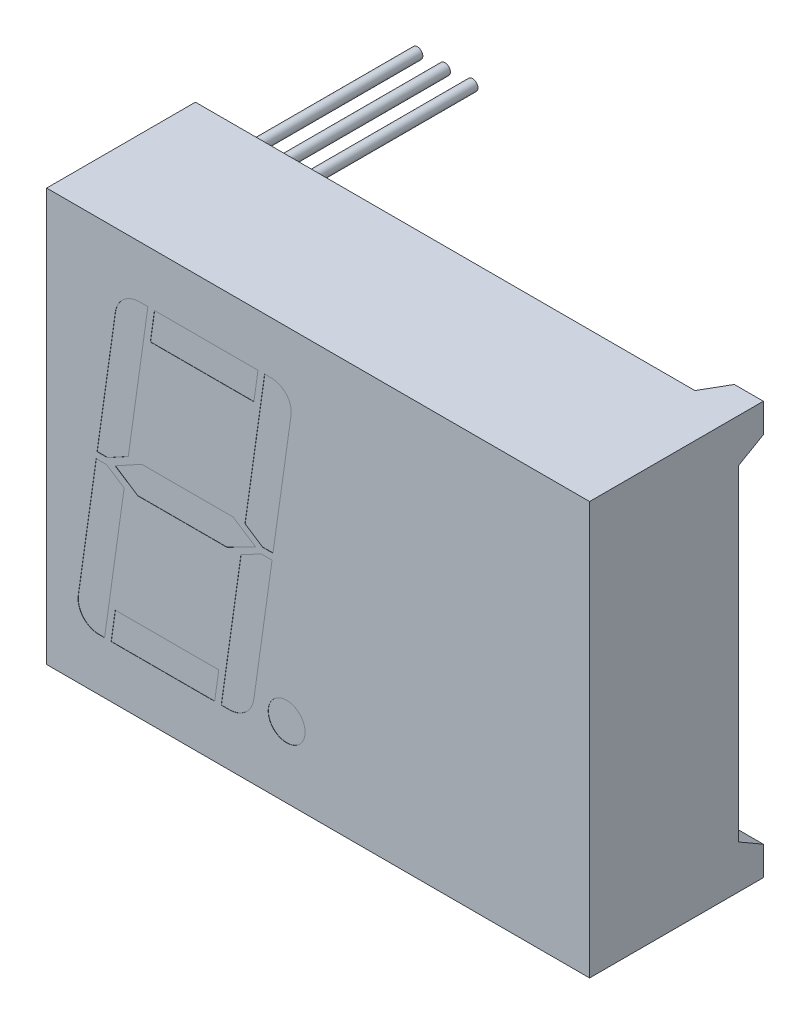
SolidWorks part; units mm, degrees
ref_plane "Plan de face" through (0, 0, 0) normal (0, 0, 1) x (1, 0, 0)
ref_plane "Plan de dessus" through (0, 0, 0) normal (0, 1, 0) x (1, 0, 0)
ref_plane "Plan de droite" through (0, 0, 0) normal (1, 0, 0) x (0, 0, -1)
sketch "Sketch1" plane through (0, 0, 0) normal (0, 0, 1) x (1, 0, 0)
  line L1 (12.5, -9.5) -> (-12.5, -9.5)
  line L2 (12.5, -9.5) -> (12.5, 9.5)
  line L3 (12.5, 9.5) -> (-12.5, 9.5)
  line L4 (-12.5, -9.5) -> (-12.5, 9.5)
  line L5 (12.5, -9.5) -> (-12.5, 9.5) construction
  line L6 (12.5, 9.5) -> (-12.5, -9.5) construction
  point P0 (0, 0)
  dimension "D1" = 25
  dimension "D2" = 19
extrude "Boss-Extrude1" add sketch "Sketch1" along normal blind 8
sketch "Sketch8" plane through (12.5, 0, 0) normal (1, 0, 0) x (0, 0, -1)
  line L0 (0, 0) -> (-8, 0) construction
  line L1 (0, -9.5) -> (0, 9.5) construction
  line L2 (-8, -9.5) -> (-8, 9.5) construction
  line L3 (-1.15, 7.5) -> (-1.15, -7.5)
  line L4 (-1.15, -7.5) -> (0, -8.164)
  line L5 (0, 8.164) -> (0, -8.164)
  line L6 (-8, -9.5) -> (0, -9.5) construction
  line L7 (-1.15, 7.5) -> (0, 8.164)
  point P13 (-1.15, 0)
  dimension "D1" = 1.15
  dimension "D2" = 2
  dimension "D3" = 120
extrude "Cut-Extrude9" cut sketch "Sketch8" against normal up to next
sketch "Sketch6" plane through (0, -9.5, 0) normal (0, -1, 0) x (1, 0, 0)
  line L0 (11.164, 0) -> (10.5, 1.15)
  line L3 (-12.5, 0) -> (12.5, 0) construction
  line L4 (10.5, 1.15) -> (-12.5, 1.15)
  line L7 (-12.5, 8) -> (-12.5, 0) construction
  line L8 (-12.5, 1.15) -> (-12.5, 0)
  line L9 (-12.5, 0) -> (11.164, 0)
  line L10 (12.5, 8) -> (12.5, 0) construction
  dimension "D1" = 2
  dimension "D2" = 120
  dimension "D3" = 1.15
extrude "Cut-Extrude3" cut sketch "Sketch6" against normal up to surface (19 mm away) up to face at (0, 9.5, 4)
sketch "Sketch7" plane through (0, 0, 1.15) normal (0, 0, -1) x (-1, 0, 0)
  line L1 (12.5, 0) -> (-12.5, 0) construction
  line L6 (-12.5, 7.5) -> (-12.5, -7.5) construction
  line L8 (12.5, -9.5) -> (12.5, 9.5) construction
  circle A0 centre (9.96, 7.62) radius 0.25
  circle A1 centre (8.69, 7.62) radius 0.25
  circle A2 centre (11.23, 7.62) radius 0.25
  circle A3 centre (9.96, -7.65) radius 0.25
  circle A4 centre (8.69, -7.65) radius 0.25
  circle A5 centre (11.23, -7.65) radius 0.25
  dimension "D3" = 3
  dimension "D2" = 0.5
  dimension "D1" = 1.27
  dimension "D6" = 7.62
  dimension "D4" = 2
extrude "Boss-Extrude2" add sketch "Sketch7" along normal blind 8.95
sketch "Sketch9" plane through (0, 0, 8) normal (0, 0, 1) x (1, 0, 0)
  line L0 (-12.5, 0) -> (12.5, 0) construction
  line L1 (-12.5, 9.5) -> (-12.5, -9.5) construction
  line L2 (12.5, -9.5) -> (12.5, 9.5) construction
  line L3 (-6.15, 9.5) -> (-6.15, -9.5) construction
  line L4 (12.5, 9.5) -> (-12.5, 9.5) construction
  line L5 (-12.5, -9.5) -> (12.5, -9.5) construction
  line L6 (-9.2022, 7.1) -> (-11.1978, -7.1) construction
  line L7 (-11.1978, -7.1) -> (-3.0978, -7.1) construction
  line L8 (-3.0978, -7.1) -> (-1.1022, 7.1) construction
  line L9 (-1.1022, 7.1) -> (-9.2022, 7.1) construction
  line L10 (-5.1522, 7.1) -> (-7.1478, -7.1) construction
  line L11 (-3.5826, -7.1) -> (-1.5869, 7.1) construction
  line L12 (-1.2919, 5.75) -> (-9.3919, 5.75) construction
  line L13 (-10.7131, -7.1) -> (-8.7174, 7.1) construction
  line L14 (-9.8346, -7.1) -> (-7.8389, 7.1) construction
  line L15 (-4.4611, -7.1) -> (-2.4654, 7.1) construction
  line L16 (-2.9081, -5.75) -> (-11.0081, -5.75) construction
  line L17 (-2.0789, 0.15) -> (-10.1789, 0.15) construction
  line L18 (-2.1211, -0.15) -> (-10.2211, -0.15) construction
  line L19 (-10.1789, 0.15) -> (-9.3389, 6.1268)
  line L20 (-8.2194, 7.1) -> (-7.8389, 7.1)
  line L21 (-7.8389, 7.1) -> (-8.7419, 0.675)
  line L22 (-8.7419, 0.675) -> (-9.6942, 0.15)
  line L23 (-9.6942, 0.15) -> (-10.1789, 0.15)
  line L24 (-2.0789, 0.15) -> (-2.5636, 0.15)
  line L25 (-2.5636, 0.15) -> (-3.3684, 0.675)
  line L26 (-3.3684, 0.675) -> (-2.4654, 7.1)
  line L27 (-2.4654, 7.1) -> (-2.1419, 7.1)
  line L28 (-1.2469, 6.0704) -> (-2.0789, 0.15)
  line L29 (-2.0051, 0.675) -> (-10.1051, 0.675) construction
  line L30 (-2.1949, -0.675) -> (-10.2949, -0.675) construction
  line L31 (-10.2211, -0.15) -> (-9.7364, -0.15)
  line L32 (-9.7364, -0.15) -> (-8.9316, -0.675)
  line L33 (-8.9316, -0.675) -> (-9.8346, -7.1)
  line L34 (-9.8346, -7.1) -> (-10.1004, -7.1)
  line L35 (-11.0451, -6.0132) -> (-10.2211, -0.15)
  line L36 (-2.1211, -0.15) -> (-2.9581, -6.1055)
  line L37 (-4.1022, -7.1) -> (-4.4611, -7.1)
  line L38 (-4.4611, -7.1) -> (-3.5528, -0.6372)
  line L39 (-3.5528, -0.6372) -> (-2.6058, -0.15)
  line L40 (-2.6058, -0.15) -> (-2.1211, -0.15)
  line L41 (-9.3419, -5.75) -> (-4.5743, -5.75)
  line L42 (-4.5743, -5.75) -> (-4.7641, -7.1)
  line L43 (-4.7641, -7.1) -> (-9.5316, -7.1)
  line L44 (-9.5316, -7.1) -> (-9.3419, -5.75)
  line L45 (-7.5359, 7.1) -> (-2.7684, 7.1)
  line L46 (-2.7684, 7.1) -> (-2.9581, 5.75)
  line L47 (-2.9581, 5.75) -> (-7.7257, 5.75)
  line L48 (-7.7257, 5.75) -> (-7.5359, 7.1)
  line L49 (-8.1205, 0.675) -> (-3.9175, 0.675)
  line L50 (-3.9175, 0.675) -> (-2.8828, 0)
  line L51 (-2.8828, 0) -> (-4.1948, -0.675)
  line L52 (-4.1948, -0.675) -> (-8.3102, -0.675)
  line L53 (-8.3102, -0.675) -> (-9.3449, 0)
  line L54 (-9.3449, 0) -> (-8.1205, 0.675)
  circle A0 centre (-1.45, -6.25) radius 0.85
  arc A1 (-9.3389, 6.1268) -> (-8.2194, 7.1) centre (-8.2194, 5.9695) cw
  arc A2 (-2.1419, 7.1) -> (-1.2469, 6.0704) centre (-2.1419, 6.1962) cw
  arc A3 (-10.1004, -7.1) -> (-11.0451, -6.0132) centre (-10.1004, -6.146) cw
  arc A4 (-2.9581, -6.1055) -> (-4.1022, -7.1) centre (-4.1022, -5.9447) cw
  point P6 (-6.15, 0)
  point P15 (-10.2, 0)
  point P21 (-6.15, 0)
  point P26 (-2.5847, 0)
  point P31 (-9.7153, 0)
  point P32 (-5.3419, 5.75)
  point P35 (-8.8367, 0)
  point P38 (-3.4633, 0)
  point P41 (-6.9581, -5.75)
  point P44 (-6.1289, 0.15)
  point P47 (-6.1711, -0.15)
  point P60 (-6.0551, 0.675)
  point P63 (-6.2449, -0.675)
  dimension "D4" = 1.7
  dimension "D1" = 6.35
  dimension "D2" = 8.1
  dimension "D3" = 14.2
  dimension "D5" = 4.7
  dimension "D6" = 0.48
  dimension "D7" = 1.35
  dimension "D8" = 0.48
  dimension "D9" = 1.35
  dimension "D10" = 1.35
  dimension "D11" = 1.35
  dimension "D12" = 0.15
  dimension "D13" = 0.15
  dimension "D14" = 0.675
  dimension "D15" = 0.675
  dimension "D16" = 0.3
  dimension "D17" = 0.3
  dimension "D18" = 0.3
  dimension "D19" = 0.3
  dimension "D20" = 8
  dimension "D21" = 0.3
  dimension "D22" = 0.3
extrude "Cut-Extrude10" cut sketch "Sketch9" against normal blind 0.01
